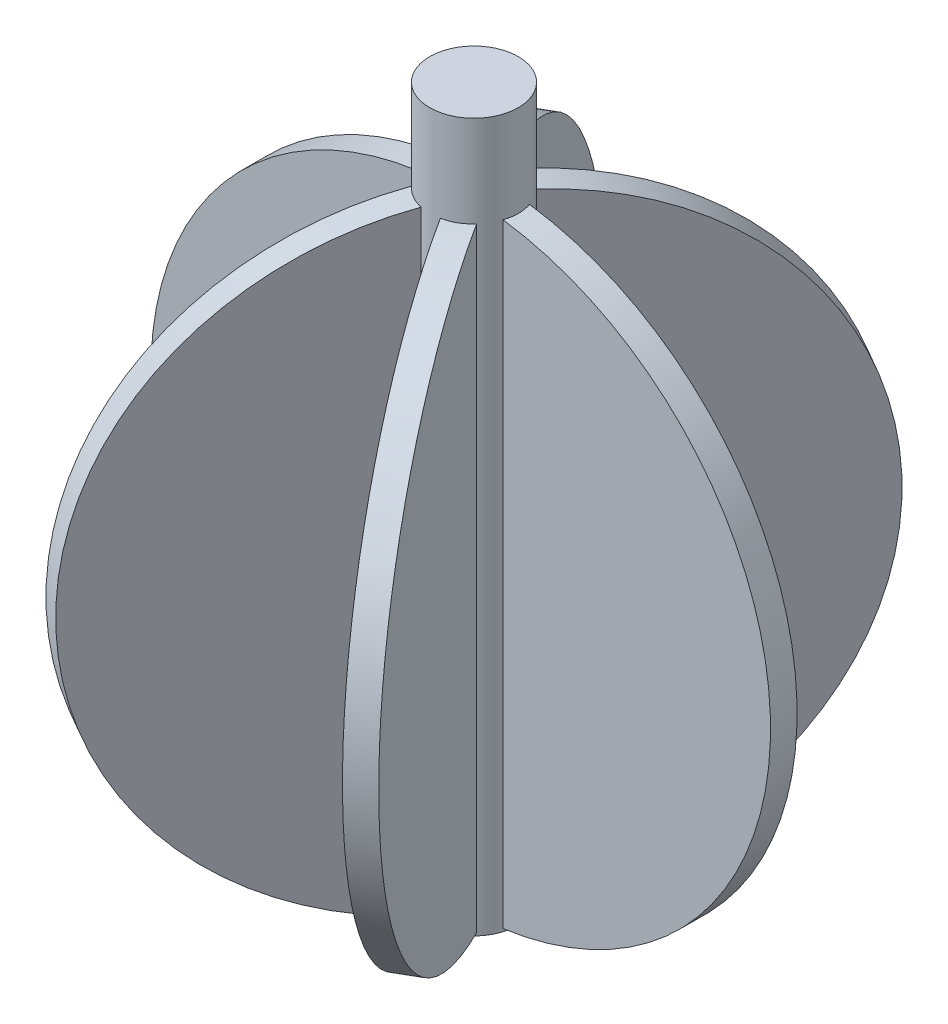
SolidWorks part; units mm, degrees
ref_plane "Front Plane" through (0, 0, 0) normal (0, 0, 1) x (1, 0, 0)
ref_plane "Top Plane" through (0, 0, 0) normal (0, 1, 0) x (1, 0, 0)
ref_plane "Right Plane" through (0, 0, 0) normal (1, 0, 0) x (0, 0, -1)
sketch "Sketch2" plane through (0, 0, 0) normal (0, 1, 0) x (1, 0, 0)
  circle A0 centre (0, 0) radius 5
  dimension "D1" = 10
extrude "Boss-Extrude1" add sketch "Sketch2" along normal blind 80
sketch "Sketch3" plane through (0, 0, 0) normal (0, 0, 1) x (1, 0, 0)
  line L0 (0, 0) -> (0, 80) construction
  line L1 (5, 80) -> (-5, 80) construction
  line L5 (0, 70) -> (0, 0)
  arc A0 (0, 0) -> (0, 70) centre (0, 35) ccw
  dimension "D1" = 70
extrude "Boss-Extrude2" add sketch "Sketch3" along normal blind 1.5 and the other way blind 1.5
pattern_circular "CirPattern1" count 6 every 60 about axis through (0, 80, 0) along (0, -1, 0) of "Boss-Extrude2"
sketch "Sketch4" plane through (0, 0, 0) normal (0, -1, 0) x (1, 0, 0)
  line L0 (-0.5, 1.4142) -> (-0.5, -1.4142)
  line L1 (0, 5) -> (0, -5) construction
  arc A0 (-0.5, -1.4142) -> (-0.5, 1.4142) centre (0, 0) ccw
  circle A2 centre (0, 0) radius 5 construction
  dimension "D1" = 3
  dimension "D2" = 0.5
extrude "Cut-Extrude1" cut sketch "Sketch4" against normal blind 10
